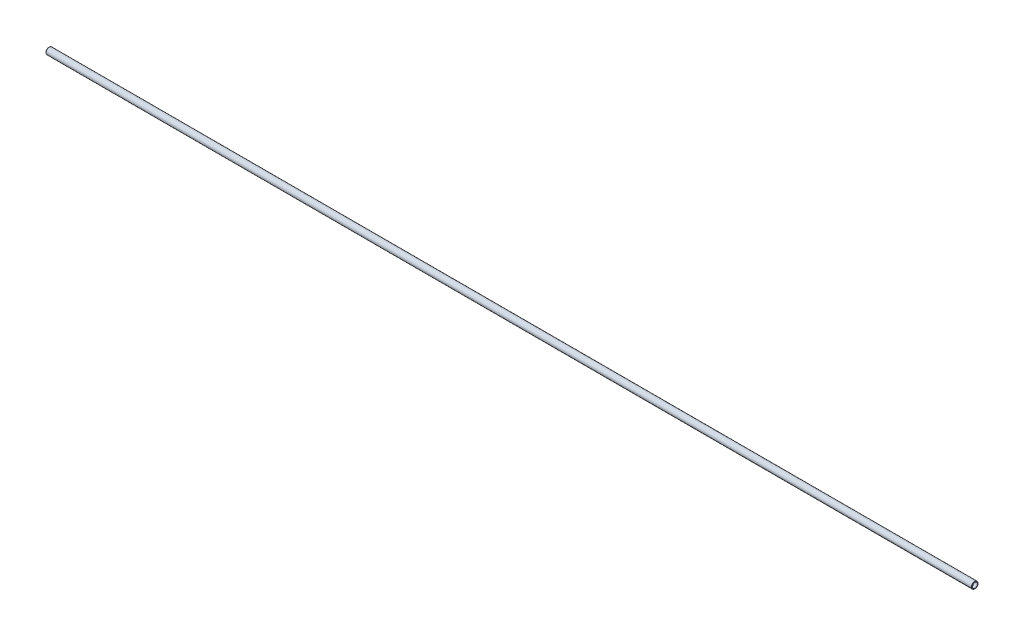
SolidWorks part; units mm, degrees
material "Cast Alloy Steel"
ref_plane "Front Plane" through (0, 0, 0) normal (0, 0, 1) x (1, 0, 0)
ref_plane "Top Plane" through (0, 0, 0) normal (0, 1, 0) x (1, 0, 0)
ref_plane "Right Plane" through (0, 0, 0) normal (1, 0, 0) x (0, 0, -1)
ref_plane "Plane1" through (1288.7706, 0, 0) normal (1, 0, 0) x (0, 0, -1)
sketch "Sketch1" plane through (0, 0, 0) normal (0, 0, 1) x (1, 0, 0)
  line L0 (-0.445, 3.6899) -> (-0.2794, 3.5242)
  line L1 (-0.2794, 3.5242) -> (0, 3.5242)
  line L2 (0, 3.5242) -> (0.5588, 4.0831)
  line L3 (0.5588, 4.0831) -> (1288.2118, 4.0831)
  line L4 (1288.2118, 4.0831) -> (1288.7706, 3.5242)
  line L5 (1288.7706, 3.5242) -> (1289.05, 3.5242)
  line L6 (1289.05, 3.5242) -> (1289.2156, 3.6899)
  line L7 (1289.2156, 3.8695) -> (1288.6895, 4.3956)
  line L8 (1288.2943, 4.5593) -> (0.4762, 4.5593)
  line L9 (0.0811, 4.3956) -> (-0.445, 3.8695)
  line L10 (1288.7706, 0) -> (0, 0) construction
  arc A0 (-0.445, 3.8695) -> (-0.445, 3.6899) centre (-0.3552, 3.7797) ccw
  arc A1 (1289.2156, 3.6899) -> (1289.2156, 3.8695) centre (1289.1258, 3.7797) ccw
  arc A2 (1288.6895, 4.3956) -> (1288.2943, 4.5593) centre (1288.2944, 4.0005) ccw
  arc A3 (0.4762, 4.5593) -> (0.0811, 4.3956) centre (0.4762, 4.0005) ccw
revolve "Revolve1" add sketch "Sketch1" angle 360 about L10 reverse direction yes
ref_plane "Plane2" through (644.3853, 0, 0) normal (1, 0, 0) x (0, 0, -1)
ref_plane "cp1 XY" through (644.3853, 0, 0) normal (1, 0, 0) x (0, 0, -1)
ref_plane "cp1 XZ" through (0, 4.5593, 0) normal (0, -1, 0) x (-1, 0, 0)
ref_plane "cp1 YZ" through (0, 0, 0) normal (0, 0, -1) x (-1, 0, 0)
ref_axis "cp1 X" through (644.3853, 4.5593, 80.9) along (0, 0, -1)
ref_axis "cp1 Y" through (644.3853, -50, 0) along (0, 1, 0)
ref_axis "cp1 Z" through (80.9, 4.5593, 0) along (-1, 0, 0)
sketch3d "cp1"
  point P0 (644.3853, 4.5593, 0)
ref_plane "cp2 XY" through (644.3853, 0, 0) normal (1, 0, 0) x (0, 0, -1)
ref_plane "cp2 XZ" through (0, 0, 0) normal (0, -1, 0) x (-1, 0, 0)
ref_plane "cp2 YZ" through (0, 0, -4.5593) normal (0, 0, -1) x (-1, 0, 0)
ref_axis "cp2 X" through (644.3853, 0, 80.9) along (0, 0, -1)
ref_axis "cp2 Y" through (644.3853, -50, -4.5593) along (0, 1, 0)
ref_axis "cp2 Z" through (80.9, 0, -4.5593) along (-1, 0, 0)
sketch3d "cp2"
  point P0 (644.3853, 0, -4.5593)
ref_plane "cp3 XY" through (644.3853, 0, 0) normal (1, 0, 0) x (0, 0, -1)
ref_plane "cp3 XZ" through (0, -4.5593, 0) normal (0, -1, 0) x (-1, 0, 0)
ref_plane "cp3 YZ" through (0, 0, 0) normal (0, 0, -1) x (-1, 0, 0)
ref_axis "cp3 X" through (644.3853, -4.5593, 80.9) along (0, 0, -1)
ref_axis "cp3 Y" through (644.3853, -50, 0) along (0, 1, 0)
ref_axis "cp3 Z" through (80.9, -4.5593, 0) along (-1, 0, 0)
sketch3d "cp3"
  point P0 (644.3853, -4.5593, 0)
ref_plane "cp4 XY" through (644.3853, 0, 0) normal (1, 0, 0) x (0, 0, -1)
ref_plane "cp4 XZ" through (0, 0, 0) normal (0, -1, 0) x (-1, 0, 0)
ref_plane "cp4 YZ" through (0, 0, 4.5593) normal (0, 0, -1) x (-1, 0, 0)
ref_axis "cp4 X" through (644.3853, 0, 80.9) along (0, 0, -1)
ref_axis "cp4 Y" through (644.3853, -50, 4.5593) along (0, 1, 0)
ref_axis "cp4 Z" through (80.9, 0, 4.5593) along (-1, 0, 0)
sketch3d "cp4"
  point P0 (644.3853, 0, 4.5593)
ref_plane "tube_front XY" through (0, 0, 0) normal (1, 0, 0) x (0, 0, -1)
ref_plane "tube_front XZ" through (0, 0, 0) normal (0, -1, 0) x (-1, 0, 0)
ref_plane "tube_front YZ" through (0, 0, 0) normal (0, 0, -1) x (-1, 0, 0)
ref_axis "tube_front X" through (0, 0, 80.9) along (0, 0, -1)
ref_axis "tube_front Y" through (0, -50, 0) along (0, 1, 0)
ref_axis "tube_front Z" through (80.9, 0, 0) along (-1, 0, 0)
sketch3d "tube_front"
  point P0 (0, 0, 0)
ref_plane "tube_rear XY" through (1288.7706, 0, 0) normal (1, 0, 0) x (0, 0, -1)
ref_plane "tube_rear XZ" through (0, 0, 0) normal (0, -1, 0) x (-1, 0, 0)
ref_plane "tube_rear YZ" through (0, 0, 0) normal (0, 0, -1) x (-1, 0, 0)
ref_axis "tube_rear X" through (1288.7706, 0, 80.9) along (0, 0, -1)
ref_axis "tube_rear Y" through (1288.7706, -50, 0) along (0, 1, 0)
ref_axis "tube_rear Z" through (80.9, 0, 0) along (-1, 0, 0)
sketch3d "tube_rear"
  point P0 (1288.7706, 0, 0)
